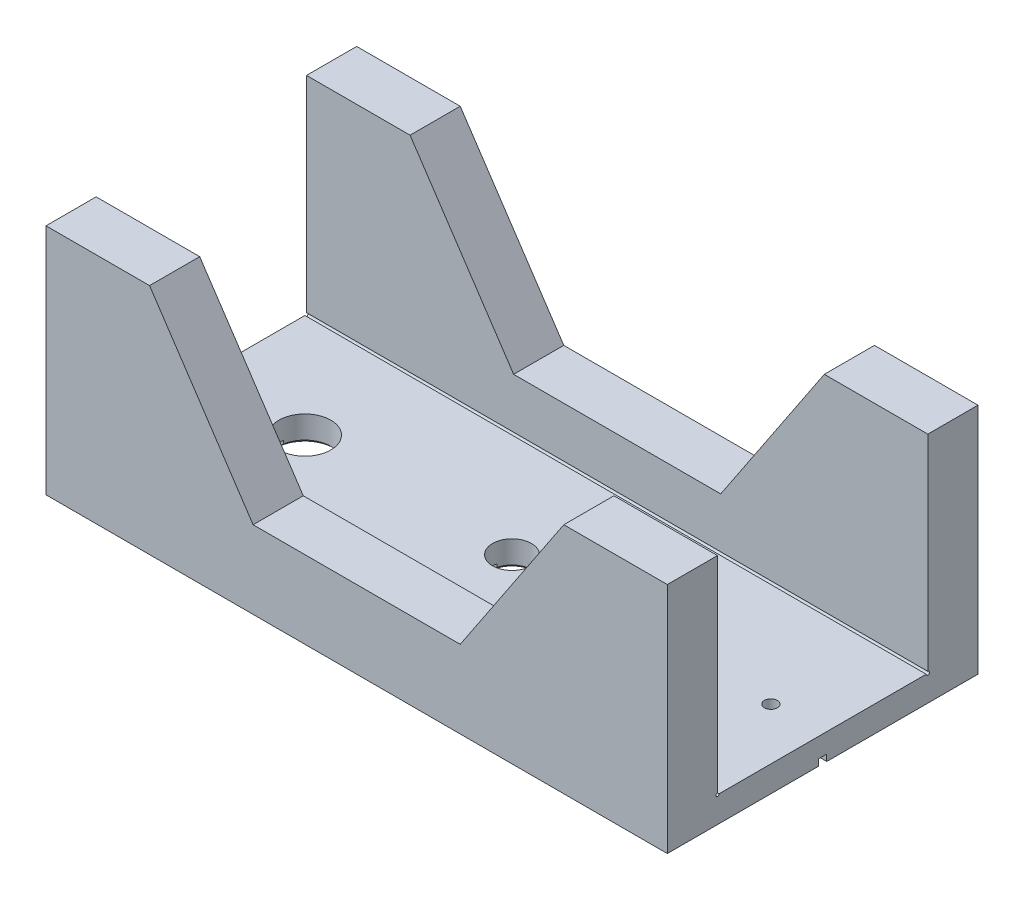
SolidWorks part; units mm, degrees
ref_plane "Front Plane" through (0, 0, 0) normal (0, 0, 1) x (1, 0, 0)
ref_plane "Top Plane" through (0, 0, 0) normal (0, 1, 0) x (1, 0, 0)
ref_plane "Right Plane" through (0, 0, 0) normal (1, 0, 0) x (0, 0, -1)
sketch "Sketch2" plane through (0, 0, 0) normal (0, 1, 0) x (1, 0, 0)
  line L0 (-76.2, 19.05) -> (0, 19.05) construction
  line L1 (0, 0) -> (-76.2, 0)
  line L2 (0, 0) -> (0, 38.1)
  line L3 (0, 38.1) -> (-76.2, 38.1)
  line L4 (-76.2, 0) -> (-76.2, 38.1)
  line L5 (-76.2, 6.15) -> (0, 6.15)
  line L6 (-76.2, 31.95) -> (0, 31.95)
  dimension "D1" = 38.1
  dimension "D2" = 76.2
  dimension "D3" = 6.15
extrude "Boss-Extrude1" add sketch "Sketch2" along normal blind 28.575 contours L4 L6 L2 L3 | L5 L4 L1 L2 region at (-38.1, 0, -3.075) region at (-38.1, 0, -35.025)
extrude "Boss-Extrude2" add sketch "Sketch2<3>" along normal blind 3.175 contours L4 L0 L2 L6 | L0 L4 L5 L2 region at (-38.1, 0, -25.5) region at (-38.1, 0, -12.6)
sketch "Sketch2<3>" plane through (0, 0, 0) normal (0, 1, 0) x (1, 0, 0) same geometry as "Sketch2"
sketch "Sketch3" plane through (0, 0, 0) normal (0, 0, 1) x (1, 0, 0)
  line L0 (-38.1, 28.575) -> (-38.1, 9.525) construction
  line L1 (0, 28.575) -> (-76.2, 28.575) construction
  line L2 (-25.4, 9.525) -> (-50.8, 9.525)
  line L3 (-50.8, 9.525) -> (-63.5, 28.575)
  line L4 (-76.2, 28.575) -> (-76.2, 0) construction
  line L5 (-25.4, 9.525) -> (-12.7, 28.575)
  line L6 (-12.7, 28.575) -> (-63.5, 28.575)
  line L7 (-63.5, 28.575) -> (-12.7, 28.575)
  point P6 (-38.1, 9.525)
  line M6 (0, 28.575) -> (-76.2, 28.575)
  dimension "D1" = 19.05
  dimension "D2" = 25.4
  dimension "D3" = 12.7
extrude "Cut-Extrude2" cut sketch "Sketch3" against normal through all contours L0 L7 L3 L2 | L0 L2 L5 M6 region at (-28.2222, 20.1083, 0) region at (-47.9778, 20.1083, 0)
sketch "Sketch4" plane through (0, 0, 0) normal (0, -1, 0) x (1, 0, 0)
  line L0 (-76.2, -19.05) -> (0, -19.05) construction
  line L1 (-76.2, 0) -> (-76.2, -38.1) construction
  line L2 (0, 0) -> (0, -38.1) construction
  circle A0 centre (-63.5, -19.05) radius 3.175
  circle A1 centre (-38.1, -19.05) radius 2.3812
  circle A2 centre (-19.05, -19.05) radius 1.5875
  circle A3 centre (-6.35, -19.05) radius 0.7938
  dimension "D1" = 12.7
  dimension "D2" = 19.05
  dimension "D3" = 6.35
extrude "Cut-Extrude3" cut sketch "Sketch4" against normal through all
sketch "Sketch5" plane through (0, 0, 0) normal (1, 0, 0) x (0, 0, -1)
  circle A0 centre (6.15, 3.175) radius 0.2
  circle A1 centre (31.95, 3.175) radius 0.2
extrude "Cut-Extrude4" cut sketch "Sketch5" against normal through all
chamfer "Chamfer1" distance 0.4 angle 45 4 edges at (-6.35, 0, -19.8437) (-19.05, 0, -20.6375) (-38.1, 0, -21.4312) (-63.5, 0, -22.225)
sketch "Sketch6" plane through (0, 0, 0) normal (0, -1, 0) x (-1, 0, 0)
  line L0 (76.2, 19.05) -> (0, 19.05) construction
  line L1 (76.2, 0) -> (76.2, 38.1) construction
  line L2 (0, 0) -> (0, 38.1) construction
  line L4 (0, 19.55) -> (76.2, 19.55)
  line L5 (0, 19.55) -> (0, 18.55)
  line L6 (0, 18.55) -> (76.2, 18.55)
  line L7 (76.2, 19.55) -> (76.2, 18.55)
  line L8 (0, 19.55) -> (76.2, 18.55) construction
  line L9 (0, 18.55) -> (76.2, 19.55) construction
  point P6 (38.1, 19.05)
  dimension "D1" = 1
extrude "Cut-Extrude5" cut sketch "Sketch6" against normal blind 0.7937
